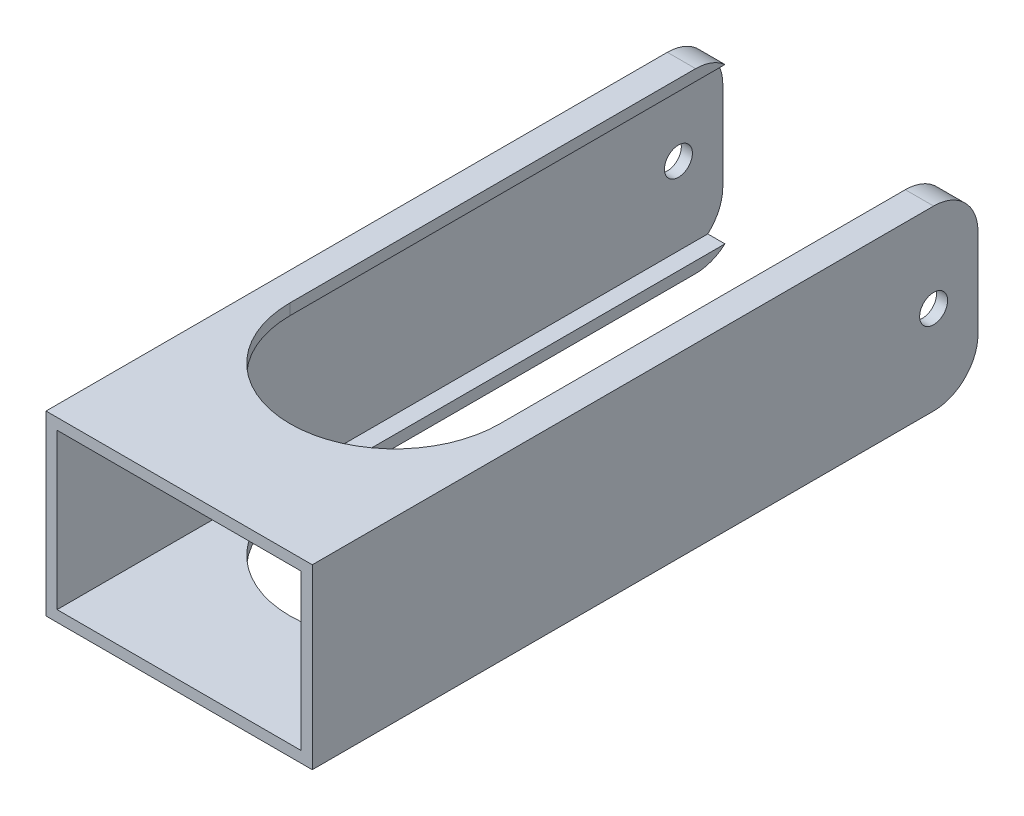
SolidWorks part; units mm, degrees
material "6061 Alloy"
ref_plane "Front Plane" through (0, 0, 0) normal (0, 0, 1) x (1, 0, 0)
ref_plane "Top Plane" through (0, 0, 0) normal (0, 1, 0) x (1, 0, 0)
ref_plane "Right Plane" through (0, 0, 0) normal (1, 0, 0) x (0, 0, -1)
sketch "Sketch1" plane through (0, 0, 0) normal (0, 0, 1) x (1, 0, 0)
  line L0 (38.1, 0) -> (34.925, 0) construction
  line L1 (-38.1, 0) -> (38.1, 0) construction
  line L2 (0, 25.4) -> (0, -25.4)
  point P7 (0, 0)
sketch "Sketch2" plane through (0, 0, 0) normal (1, 0, 0) x (0, 0, -1)
  line L0 (95.25, 0) -> (-95.25, 0)
  point P4 (0, 0)
  dimension "Length" = 190.5
sketch "Sketch3" plane through (0, 0, 0) normal (0, 0, 1) x (1, 0, 0)
  line L0 (-38.1, 0) -> (38.1, 0) construction
  line L5 (38.1, -25.4) -> (-38.1, -25.4)
  line L6 (38.1, -25.4) -> (38.1, 25.4)
  line L11 (38.1, 25.4) -> (-38.1, 25.4)
  line L12 (-38.1, -25.4) -> (-38.1, 25.4)
  line L14 (38.1, -25.4) -> (-38.1, 25.4) construction
  line L15 (38.1, 25.4) -> (-38.1, -25.4) construction
  line L16 (34.925, -22.225) -> (-34.925, -22.225)
  line L17 (34.925, -22.225) -> (34.925, 22.225)
  line L18 (34.925, 22.225) -> (-34.925, 22.225)
  line L19 (-34.925, -22.225) -> (-34.925, 22.225)
  line L20 (34.925, -22.225) -> (-34.925, 22.225) construction
  line L21 (34.925, 22.225) -> (-34.925, -22.225) construction
  point P0 (0, 0)
  point P5 (0, 0)
  point P13 (34.925, -25.4)
  dimension "D1" = 3.175
  dimension "D4" = 50.8
  dimension "D2" = 3.175
extrude "Boss-Extrude1" add sketch "Sketch3" along normal up to vertex (95.25 mm away) and the other way up to vertex (95.25 mm away) up to point (0, 0, 95.25) other way up to point (0, 0, -95.25)
sketch "Sketch5" plane through (0, 0, 0) normal (1, 0, 0) x (0, 0, -1)
  line L0 (-95.25, 0) -> (95.25, 0) construction
  line L3 (-95.25, -25.4) -> (-95.25, 25.4) construction
  line L4 (95.25, -25.4) -> (95.25, 25.4) construction
  point P6 (-9.525, 0)
  point P7 (19.05, 0)
  point P8 (-19.05, 0)
  point P10 (9.525, 0)
  dimension "D1" = 85.725
  dimension "D2" = 114.3
  dimension "D3" = 85.725
  dimension "D4" = 114.3
sketch "Sketch6" plane through (0, 25.4, 0) normal (0, 1, 0) x (1, 0, 0)
  line L0 (-30, 95.25) -> (-30, -33.5)
  line L1 (38.1, 95.25) -> (-38.1, 95.25) construction
  line L2 (30, 95.25) -> (30, -33.5)
  line L3 (38.1, -95.25) -> (-38.1, -95.25) construction
  arc A0 (-30, -33.5) -> (30, -33.5) centre (0, -33.5) ccw
  line M4 (38.1, 95.25) -> (-38.1, 95.25)
  dimension "D1" = 31.75
  dimension "D2" = 60
extrude "Cut-Extrude1" cut sketch "Sketch6" against normal through all and the other way through all contours L0 A0 L2 M4 region at (0, 25.4, -18.9468)
sketch "Sketch7" plane through (38.1, 0, 0) normal (1, 0, 0) x (0, 0, -1)
  line L2 (95.25, -25.4) -> (95.25, 25.4) construction
  circle A0 centre (82.55, 0) radius 4
  dimension "D1" = 8
  dimension "D2" = 12.7
extrude "Cut-Extrude2" cut sketch "Sketch7" against normal through all
fillet "Fillet1" radius 12.7 4 edges at (-34.05, -25.4, -95.25) (-34.05, 25.4, -95.25) (34.05, -25.4, -95.25) (34.05, 25.4, -95.25)
equation "\"D1@Sketch3\"=\"Wall thickness@Sketch1\""
equation "\"D1@Sketch5\"=\"Width@Sketch1\"*1.125"
equation "\"D2@Sketch5\"=\"Width@Sketch1\"*1.5"
equation "\"D3@Sketch5\"=\"D1@Sketch5\""
equation "\"D4@Sketch5\"=\"D2@Sketch5\""
equation "\"D2@Sketch3\"=\"Wall Thickness@Sketch1\""
